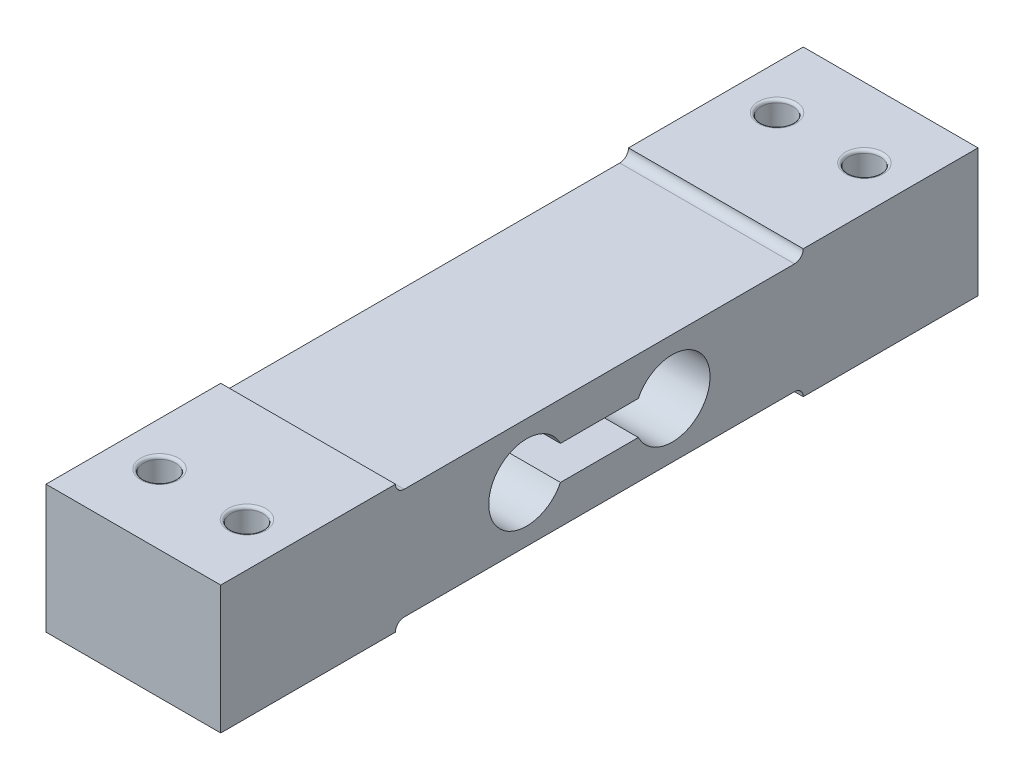
SolidWorks part; units mm, degrees
ref_plane "Front Plane" through (0, 0, 0) normal (0, 0, 1) x (1, 0, 0)
ref_plane "Top Plane" through (0, 0, 0) normal (0, 1, 0) x (1, 0, 0)
ref_plane "Right Plane" through (0, 0, 0) normal (1, 0, 0) x (0, 0, -1)
sketch "Sketch1" plane through (0, 0, 0) normal (1, 0, 0) x (0, 0, -1)
  line L1 (-65, 11) -> (65, 11)
  line L2 (-65, 11) -> (-65, -11)
  line L3 (-65, -11) -> (65, -11)
  line L4 (65, 11) -> (65, -11)
  line L5 (-65, 11) -> (65, -11) construction
  line L6 (-65, -11) -> (65, 11) construction
  line L7 (-35, 11) -> (35, 11)
  line L8 (-35, 11) -> (-35, -11)
  line L9 (-35, -11) -> (35, -11)
  line L10 (35, 11) -> (35, -11)
  line L11 (-35, 11) -> (35, -11) construction
  line L12 (-35, -11) -> (35, 11) construction
  line L13 (-35, 9.5) -> (35, 9.5)
  line L14 (-35, 9.5) -> (-35, -9.5)
  line L15 (-35, -9.5) -> (35, -9.5)
  line L16 (35, 9.5) -> (35, -9.5)
  line L17 (-35, 9.5) -> (35, -9.5) construction
  line L18 (-35, -9.5) -> (35, 9.5) construction
  line L19 (-7.6207, 2.9) -> (7.6207, 2.9)
  line L20 (-7.6207, 2.9) -> (-7.6207, -2.9)
  line L21 (-7.6207, -2.9) -> (7.6207, -2.9)
  line L22 (7.6207, 2.9) -> (7.6207, -2.9)
  line L23 (-7.6207, 2.9) -> (7.6207, -2.9) construction
  line L24 (-7.6207, -2.9) -> (7.6207, 2.9) construction
  circle A0 centre (-12.5, 0) radius 6.5
  circle A1 centre (12.5, 0) radius 6.5
  point P0 (0, 0)
  point P6 (0, 0)
  point P7 (0, 0)
  point P16 (0, 0)
  dimension "D5" = 13
  dimension "D6" = 13
  dimension "D1" = 130
  dimension "D2" = 22
  dimension "D3" = 70
  dimension "D4" = 1.5
  dimension "D7" = 5.8
  dimension "D8" = 25
  dimension "D9" = 12.5
extrude "Boss-Extrude1" add sketch "Sketch1" along normal blind 30 contours L8 L1 L2 L3 | L8 L15 L10 L13 | L1 L10 L3 L4 region at (0, 0, 50) region at (0, 0, -50) region at (0, 8.7747, 0)
fillet "Fillet1" radius 1.5 4 edges at (15, -9.5, 35) (15, -9.5, -35) (15, 9.5, -35) (15, 9.5, 35)
ref_plane "Plane1" through (15, 0, 0) normal (1, 0, 0) x (0, 0, -1)
sketch "Sketch2" plane through (0, 11, 0) normal (0, 1, 0) x (1, 0, 0)
  line L0 (30, 35) -> (0, 35) construction
  line L4 (0, 35) -> (0, 65) construction
  circle A0 centre (7.5, 53) radius 2.75
  dimension "D1" = 5.5
  dimension "D2" = 18
  dimension "D3" = 7.5
extrude "Cut-Extrude1" cut sketch "Sketch2" against normal through all
mirror "Mirror1" about plane through (15, 0, 0) normal (1, 0, 0) of "Cut-Extrude1"
mirror "Mirror2" about plane through (0, 0, 0) normal (0, 0, 1) of "Mirror1", "Cut-Extrude1"
fillet "Fillet2" radius 0.5 8 edges at (22.5, -11, 50.25) (7.5, -11, 50.25) (7.5, -11, -50.25) (22.5, -11, -50.25) (7.5, 11, -50.25) (22.5, 11, -50.25) (22.5, 11, 50.25) (7.5, 11, 50.25)
